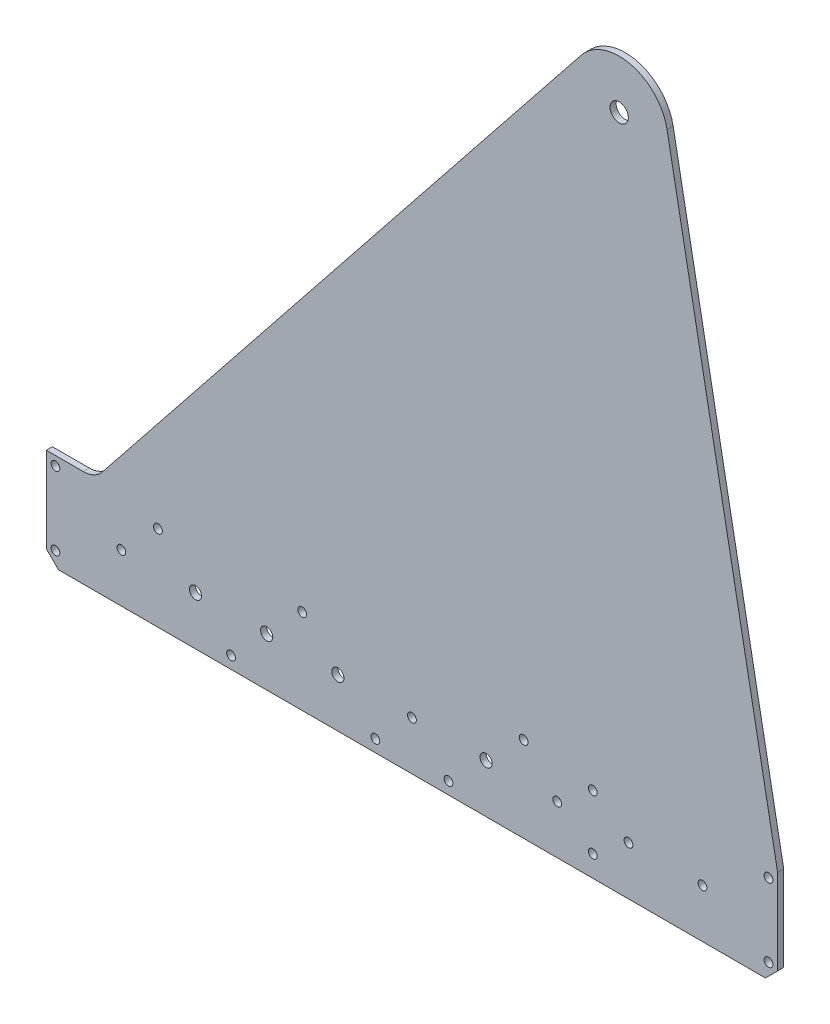
SolidWorks part; units mm, degrees
ref_plane "Front Plane" through (0, 0, 0) normal (0, 0, 1) x (1, 0, 0)
ref_plane "Top Plane" through (0, 0, 0) normal (0, 1, 0) x (1, 0, 0)
ref_plane "Right Plane" through (0, 0, 0) normal (1, 0, 0) x (0, 0, -1)
sketch "Sketch1" plane through (0, 0, 0) normal (0, 0, 1) x (1, 0, 0)
  line L1 (0, 0) -> (381, 0)
  line L2 (0, 0) -> (0, 50.8)
  line L4 (381, 0) -> (381, 50.8)
  line L5 (381, 50.8) -> (323.4127, 357.1179)
  line L6 (0, 50.8) -> (19.2844, 50.8)
  line L7 (29.2133, 55.5812) -> (278.5922, 368.2626)
  arc A0 (278.5922, 368.2626) -> (323.4127, 357.1179) centre (298.45, 352.425) cw
  arc A1 (19.2844, 50.8) -> (29.2133, 55.5812) centre (19.2844, 63.5) ccw
  point P11 (25.4, 50.8)
  dimension "D4" = 352.425
  dimension "D7" = 12.7
  dimension "D5" = 25.4
  dimension "D1" = 50.8
  dimension "D2" = 381
  dimension "D3" = 82.55
  dimension "D6" = 25.4
extrude "Boss-Extrude1" add sketch "Sketch1" along normal blind 3.175
sketch "Sketch2" plane through (0, 0, 3.175) normal (0, 0, 1) x (1, 0, 0)
  line L0 (77.724, 25.4) -> (114.808, 25.4) construction
  line L1 (190.5, 50.8) -> (190.5, 0) construction
  line L3 (0, 0) -> (381, 0) construction
  line L4 (266.192, 25.4) -> (303.276, 25.4) construction
  line L5 (0, 6.35) -> (0, 0)
  line L6 (0, 50.8) -> (0, 0) construction
  line L7 (0, 0) -> (6.35, 0)
  line L8 (6.35, 0) -> (0, 6.35)
  line L9 (381, 0) -> (374.65, 0)
  line L10 (374.65, 0) -> (381, 6.35)
  line L11 (381, 6.35) -> (381, 0)
  circle A0 centre (39.116, 25.4) radius 2.286
  circle A1 centre (190.5, 25.4) radius 2.286
  circle A2 centre (114.808, 25.4) radius 3.175
  circle A3 centre (77.724, 25.4) radius 3.175
  circle A4 centre (151.892, 25.4) radius 3.175
  circle A5 centre (229.108, 25.4) radius 3.175
  circle A6 centre (303.276, 25.4) radius 2.286
  circle A7 centre (266.192, 25.4) radius 2.286
  circle A8 centre (341.884, 25.4) radius 2.286
  circle A9 centre (58.166, 44.45) radius 2.286
  circle A10 centre (171.45, 6.35) radius 2.286
  circle A11 centre (209.55, 6.35) radius 2.286
  circle A13 centre (133.35, 44.45) radius 2.286
  circle A14 centre (248.666, 44.45) radius 2.286
  circle A15 centre (96.266, 6.35) radius 2.286
  circle A19 centre (4.7625, 46.0375) radius 2.286
  circle A20 centre (4.7625, 7.9375) radius 2.286
  circle A21 centre (376.2375, 7.9375) radius 2.286
  circle A22 centre (376.2375, 46.0375) radius 2.286
  circle A25 centre (284.734, 11.1125) radius 2.286
  circle A26 centre (284.734, 39.6875) radius 2.286
  point P17 (190.5, 25.4)
  point P38 (96.266, 25.4)
  point P49 (284.734, 25.4)
  dimension "D2" = 4.572
  dimension "D5" = 6.35
  dimension "D7" = 4.572
  dimension "D12" = 4.572
  dimension "D15" = 4.572
  dimension "D16" = 4.572
  dimension "D19" = 4.572
  dimension "D21" = 6.35
  dimension "D27" = 4.572
  dimension "D8" = 4.572
  dimension "D3" = 38.608
  dimension "D4" = 46.0375
  dimension "D6" = 14.2875
  dimension "D14" = 39.6875
  dimension "D22" = 6.35
  dimension "D25" = 4.7625
  dimension "D28" = 7.9375
extrude "Cut-Extrude1" cut sketch "Sketch2" against normal up to next
sketch "Sketch3" plane through (0, 0, 3.175) normal (0, 0, 1) x (1, 0, 0)
  circle A0 centre (298.45, 352.425) radius 4.7625
  dimension "D1" = 9.525
extrude "Cut-Extrude2" cut sketch "Sketch3" against normal through all
